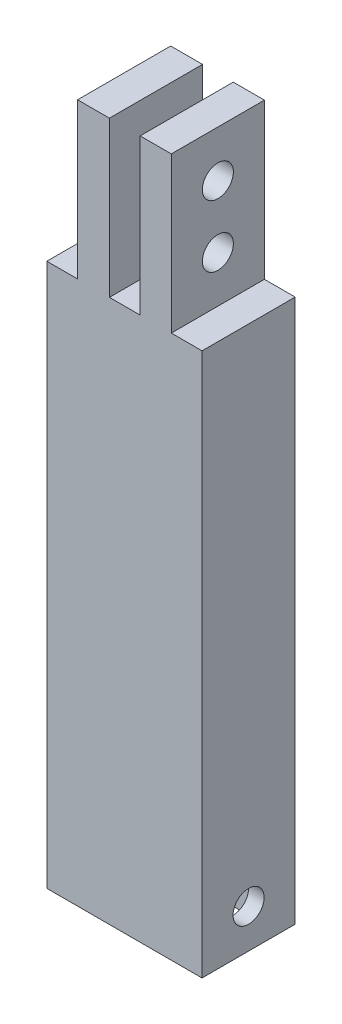
SolidWorks part; units mm, degrees
ref_plane "Front Plane" through (0, 0, 0) normal (0, 0, 1) x (1, 0, 0)
ref_plane "Top Plane" through (0, 0, 0) normal (0, 1, 0) x (1, 0, 0)
ref_plane "Right Plane" through (0, 0, 0) normal (1, 0, 0) x (0, 0, -1)
sketch "Sketch1" plane through (0, 0, 0) normal (0, 1, 0) x (1, 0, 0)
  line L1 (0, 0) -> (50, 0)
  line L2 (0, 0) -> (0, 30)
  line L3 (0, 30) -> (50, 30)
  line L4 (50, 0) -> (50, 30)
  dimension "D1" = 30
  dimension "D2" = 50
extrude "Boss-Extrude1" add sketch "Sketch1" along normal blind 225
sketch "Sketch2" plane through (0, 0, 0) normal (0, 0, 1) x (1, 0, 0)
  line L0 (0, 225) -> (50, 225) construction
  line L1 (0, 225) -> (9.9, 225)
  line L2 (0, 225) -> (0, 175)
  line L3 (0, 175) -> (9.9, 175)
  line L4 (9.9, 225) -> (9.9, 175)
  line L5 (50, 225) -> (40.1, 225)
  line L6 (50, 225) -> (50, 175)
  line L7 (50, 175) -> (40.1, 175)
  line L8 (40.1, 225) -> (40.1, 175)
  line L9 (20.1605, 225) -> (30.0605, 225)
  line L10 (20.1605, 225) -> (20.1605, 175)
  line L11 (20.1605, 175) -> (30.0605, 175)
  line L12 (30.0605, 225) -> (30.0605, 175)
  dimension "D1" = 9.9
  dimension "D2" = 9.9
  dimension "D3" = 9.9
  dimension "D4" = 50
  dimension "D5" = 50
  dimension "D6" = 50
extrude "Cut-Extrude1" cut sketch "Sketch2" against normal blind 175
sketch "Sketch3" plane through (9.9, 0, 0) normal (-1, 0, 0) x (0, 0, 1)
  line L0 (-30, 225) -> (0, 225) construction
  line L1 (0, 175) -> (0, 225) construction
  line L2 (-30, 175) -> (0, 175) construction
  circle A0 centre (-15, 210) radius 5
  circle A1 centre (-15, 190) radius 5
  dimension "D1" = 10
  dimension "D2" = 10
  dimension "D4" = 15
  dimension "D5" = 15
  dimension "D6" = 15
  dimension "D3" = 15
extrude "Cut-Extrude2" cut sketch "Sketch3" against normal blind 175
sketch "Sketch4" plane through (0, 0, 0) normal (0, -1, 0) x (1, 0, 0)
  line L0 (0, -30) -> (0, 0) construction
  line L1 (5, -25) -> (45, -25)
  line L2 (5, -25) -> (5, -5)
  line L3 (5, -5) -> (45, -5)
  line L4 (45, -25) -> (45, -5)
  line L5 (50, -30) -> (0, -30) construction
  line L6 (50, 0) -> (50, -30) construction
  line L7 (0, 0) -> (50, 0) construction
  point P6 (0, -15)
  dimension "D1" = 5
  dimension "D2" = 5
  dimension "D3" = 5
  dimension "D4" = 5
extrude "Cut-Extrude3" cut sketch "Sketch4" against normal blind 25
sketch "Sketch5" plane through (0, 0, 0) normal (-1, 0, 0) x (0, 0, 1)
  line L0 (0, 175) -> (0, 0) construction
  line L1 (-30, 0) -> (0, 0) construction
  circle A0 centre (-15, 12.5) radius 5
  dimension "D1" = 10
  dimension "D2" = 15
  dimension "D3" = 12.5
extrude "Cut-Extrude4" cut sketch "Sketch5" against normal through all
sketch "Sketch6" plane through (0, 25, 0) normal (0, -1, 0) x (1, 0, 0)
  line L0 (50, 0) -> (50, -30) construction
  line L1 (0, 0) -> (50, 0) construction
  circle A0 centre (25, -15) radius 6
  dimension "D1" = 12
  dimension "D2" = 25
  dimension "D3" = 15
extrude "Cut-Extrude5" cut sketch "Sketch6" against normal blind 40
thread "Thread1" pitch 1.5 method extrude profile "Thread Profile1" start angle 0, offset 0, length 35, pitch 1.5, diameter 12
ref_plane "Plane1" through (31, 25, -15) normal (0, 0, 1) x (1, 0, 0)
sketch "Thread Profile1" plane through (31, 25, -15) normal (0, 0, 1) x (1, 0, 0)
  line L0 (0, 0) -> (0, 1.5) construction
  line L11 (0, 0) -> (0, 1.3125)
  line L12 (0, 1.3125) -> (-0.8119, 0.8437)
  line L13 (-0.8119, 0.8437) -> (-0.8119, 0.4687)
  line L15 (-0.8119, 0.4687) -> (0, 0)
  line L17 (-0.8119, 0.6562) -> (0, 0.6562) construction
  point P2 (0, 0)
  dimension "Pitch" = 1.5
  dimension "Profile_Angle" = 60
  dimension "Profile_Land" = 0.375
  dimension "Profile_Height" = 0.8119
